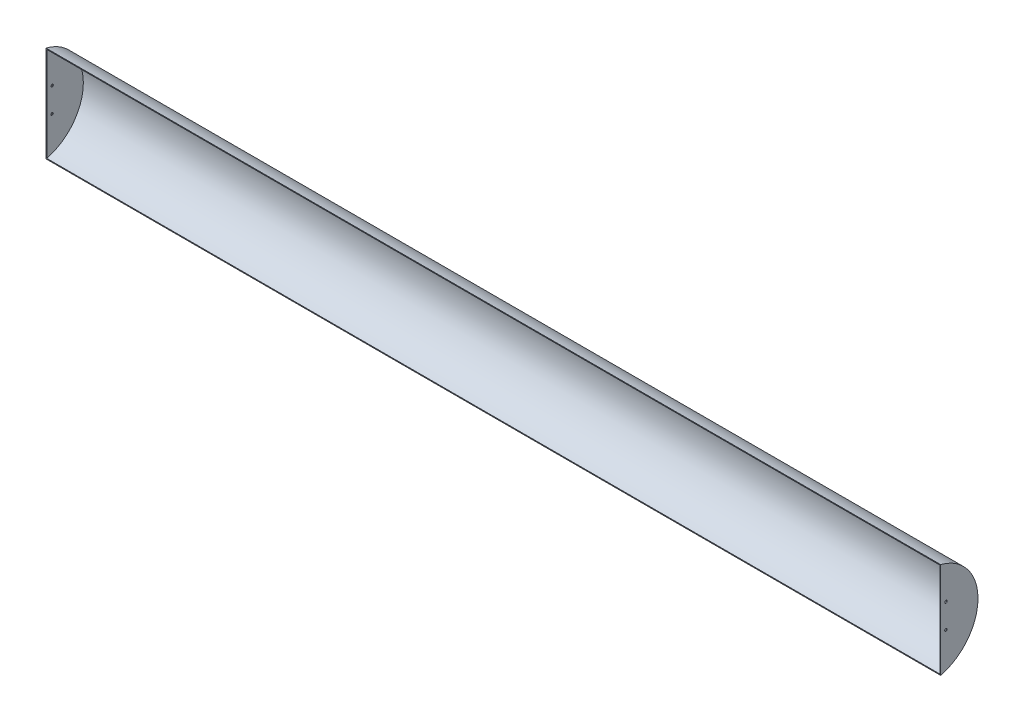
SolidWorks part; units mm, degrees
ref_plane "Front Plane" through (0, 0, 0) normal (0, 0, 1) x (1, 0, 0)
ref_plane "Top Plane" through (0, 0, 0) normal (0, 1, 0) x (1, 0, 0)
ref_plane "Right Plane" through (0, 0, 0) normal (1, 0, 0) x (0, 0, -1)
sketch "Sketch1" plane through (0, 0, 0) normal (1, 0, 0) x (0, 0, -1)
  line L0 (0, 0) -> (15, 0) construction
  line L1 (15, 58.0948) -> (15, -58.0948)
  arc A0 (15, -58.0948) -> (15, 58.0948) centre (0, 0) ccw
  dimension "D1" = 120
  dimension "D2" = 15
extrude "Boss-Extrude1" add sketch "Sketch1" along normal blind 1100 contours L1 A0
shell "Shell1" thickness 1 removed face at (550, 0, -15) outward yes
sketch "Sketch2" plane through (1101, 0, 0) normal (1, 0, 0) x (0, 0, -1)
  circle A1 centre (21.5915, 16.1774) radius 1.5
  circle A2 centre (21.4958, -13.8225) radius 1.5
extrude "Cut-Extrude1" cut sketch "Sketch2" against normal through all
